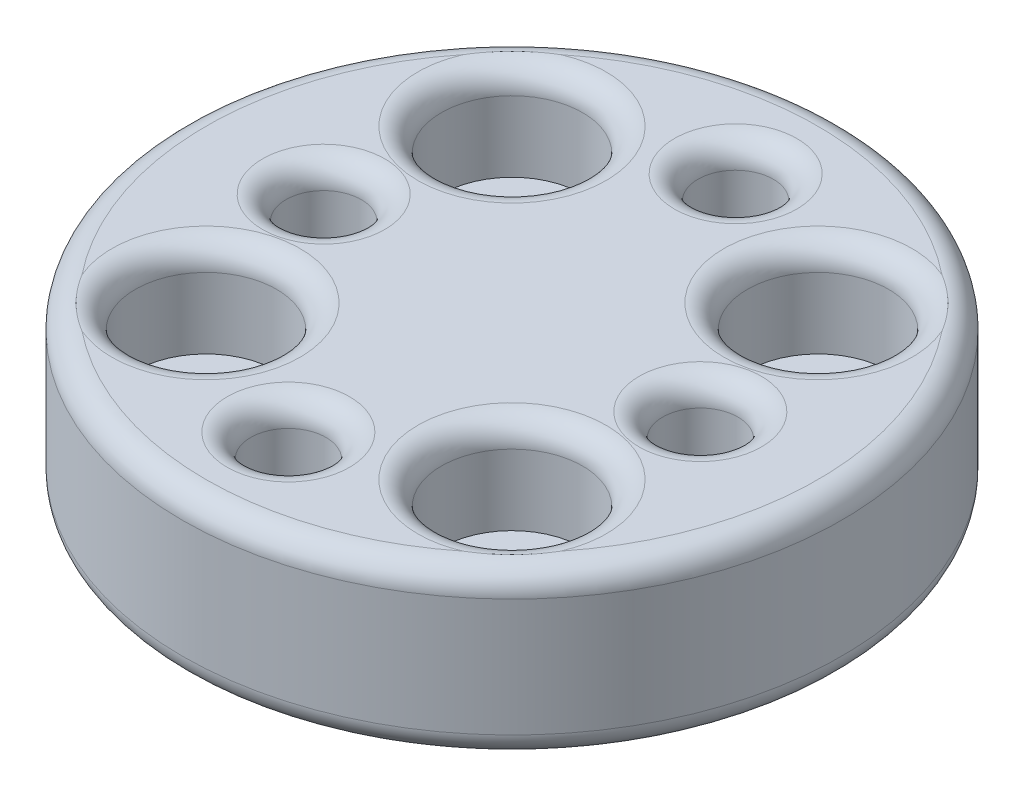
SolidWorks part; units mm, degrees
ref_plane "前视基准面" through (0, 0, 0) normal (0, 0, 1) x (1, 0, 0)
ref_plane "上视基准面" through (0, 0, 0) normal (0, 1, 0) x (1, 0, 0)
ref_plane "右视基准面" through (0, 0, 0) normal (1, 0, 0) x (0, 0, -1)
other "Configuration Table"
sketch "草图1" plane through (0, 0, 0) normal (0, 1, 0) x (1, 0, 0)
  circle A0 centre (0, 0) radius 14
  circle A1 centre (0, 9.5) radius 1.6
  circle A2 centre (8, 0) radius 1.6
  circle A3 centre (-8, 0) radius 1.6
  circle A4 centre (0, -9.5) radius 1.6
  dimension "D1" = 28
  dimension "D2" = 3.2
  dimension "D3" = 3.2
  dimension "D4" = 3.2
  dimension "D5" = 3.2
  dimension "D6" = 8
  dimension "D7" = 8
  dimension "D9" = 9.5
  dimension "D8" = 9.5
extrude "凸台-拉伸1" add sketch "草图1" along normal blind 7
sketch "草图2" plane through (0, 7, 0) normal (0, 1, 0) x (1, 0, 0)
  circle A0 centre (6.5, 6.5) radius 3
  circle A1 centre (6.5, -6.5) radius 3
  circle A2 centre (-6.5, -6.5) radius 3
  circle A3 centre (-6.5, 6.5) radius 3
  point P12 (0, 0)
  dimension "D1" = 6
  dimension "D2" = 6.5
  dimension "D3" = 6.5
  dimension "D4" = 4
extrude "切除-拉伸1" cut sketch "草图2" against normal blind 4
sketch "草图3" plane through (0, 7, 0) normal (0, 1, 0) x (1, 0, 0)
  circle A0 centre (-6.5, 6.5) radius 1.6
  circle A1 centre (6.5, 6.5) radius 1.6
  circle A2 centre (6.5, -6.5) radius 1.6
  circle A3 centre (-6.5, -6.5) radius 1.6
  point P12 (0, 0)
  dimension "D1" = 3.2
  dimension "D3" = 0
  dimension "D2" = 4
extrude "切除-拉伸2" cut sketch "草图3" against normal through all
fillet "圆角1" radius 1 18 edges at (0, 0, 11.1) (-8, 0, 1.6) (8, 0, 1.6) (0, 0, -7.9) (0, 0, 14) (-6.5, 0, -4.9) (6.5, 0, -4.9) (6.5, 0, 8.1) (-6.5, 0, 8.1) (0, 7, 11.1) (8, 7, 1.6) (0, 7, 14) (0, 7, -7.9) (-8, 7, 1.6) (6.5, 7, -3.5) (6.5, 7, 9.5) (-6.5, 7, 9.5) (-6.5, 7, -3.5)
